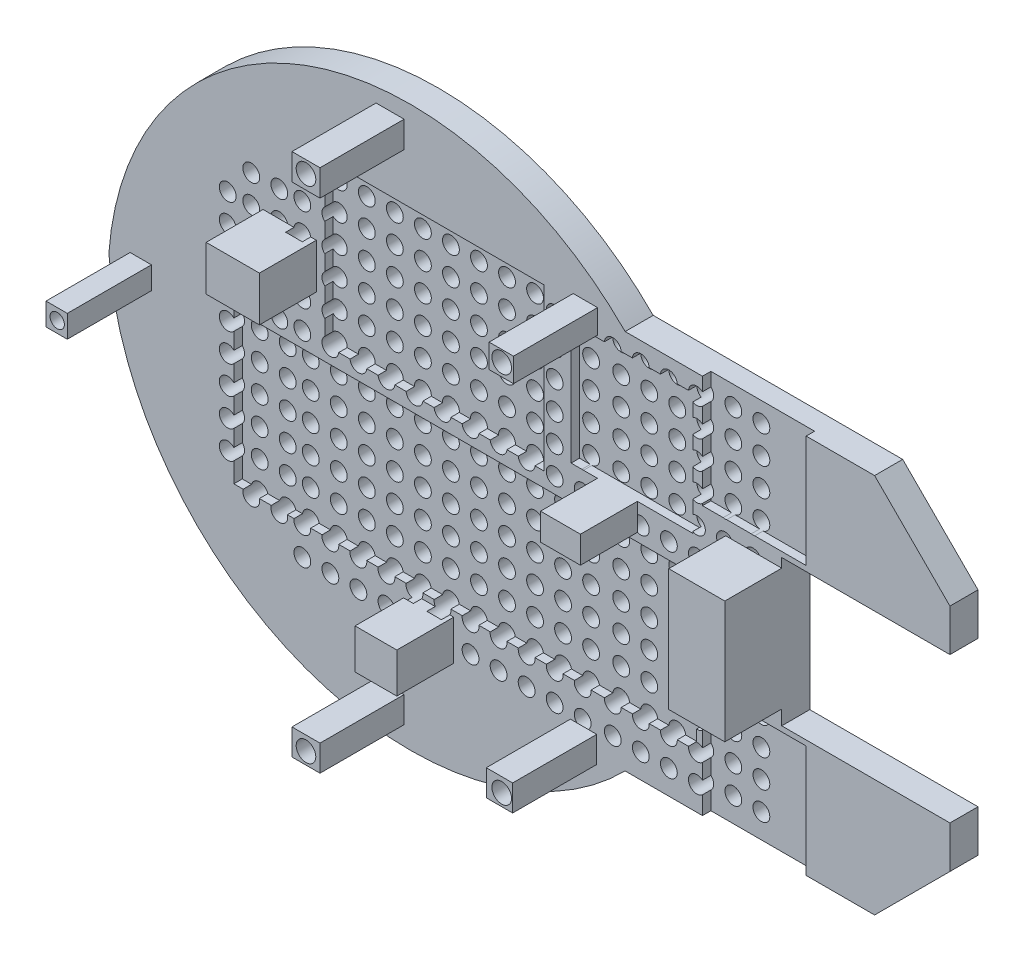
SolidWorks part; units mm, degrees
ref_plane "Front Plane" through (0, 0, 0) normal (0, 0, 1) x (1, 0, 0)
ref_plane "Top Plane" through (0, 0, 0) normal (0, 1, 0) x (1, 0, 0)
ref_plane "Right Plane" through (0, 0, 0) normal (1, 0, 0) x (0, 0, -1)
sketch "Sketch1" plane through (0, 0, 0) normal (0, 0, 1) x (1, 0, 0)
  line L1 (0, 0) -> (0, -26)
  line L2 (0, 26) -> (60, 26)
  line L3 (0, -26) -> (60, -26)
  line L4 (60, 26) -> (60, 41)
  line L5 (60, -26) -> (60, -41)
  line L6 (60, 41) -> (33.1299, 67.8701)
  line L7 (33.1299, 67.8701) -> (-55.8501, 67.8701)
  line L8 (60, -41) -> (33.1299, -67.8701)
  line L9 (33.1299, -67.8701) -> (-55.8501, -67.8701)
  line L10 (-55.8501, 67.8701) -> (-55.8501, 145.9436) construction
  line L11 (-55.8501, 145.9436) -> (-55.8501, -286.005) construction
  line L22 (0, 26) -> (0, 0)
  line L24 (-132.4482, 99.7954) -> (-270.7239, 99.7954) construction
  line L25 (-132.4482, 8.0579) -> (-132.4482, 125.9405) construction
  line L26 (-132.4482, -8.0579) -> (-132.4482, -125.1714) construction
  line L27 (-132.4482, -99.7954) -> (-270.7239, -99.7954) construction
  arc A7 (-240, 0) -> (-55.8501, 67.8701) centre (-132.4482, -8.0579) cw
  arc A8 (-55.8501, -67.8701) -> (-240, 0) centre (-132.4482, 8.0579) cw
  dimension "D11" = 199.5908
  dimension "D12" = 240
  dimension "D10" = 135.7401
  dimension "D1" = 26
  dimension "D2" = 26
  dimension "D3" = 60
  dimension "D4" = 15
  dimension "D5" = 15
  dimension "D6" = 135
  dimension "D7" = 38
  dimension "D8" = 38
  dimension "D9" = 135
  dimension "D15" = 88.98
  dimension "D16" = 88.98
extrude "Boss-Extrude1" add sketch "Sketch1" along normal blind 10 and the other way blind 0.01
sketch "Sketch3" plane through (0, 0, 10) normal (0, 0, 1) x (1, 0, 0)
  line L0 (33.1299, 67.8701) -> (-55.8501, 67.8701) construction
  line L1 (-28.273, 67.8701) -> (8.727, 67.8701)
  line L2 (-28.273, 67.8701) -> (-28.273, 27.8701)
  line L3 (-28.273, 27.8701) -> (8.727, 27.8701)
  line L4 (8.727, 67.8701) -> (8.727, 27.8701)
  dimension "D1" = 40
  dimension "D2" = 37
extrude "Cut-Extrude1" cut sketch "Sketch3" against normal blind 3 contours L2 L1 L4 L3
sketch "Sketch5" plane through (0, 0, 10) normal (0, 0, 1) x (1, 0, 0)
  line L0 (-55.8501, -67.8701) -> (33.1299, -67.8701) construction
  line L1 (-28.273, -27.8701) -> (8.727, -27.8701)
  line L2 (-28.273, -27.8701) -> (-28.273, -67.8701)
  line L3 (-28.273, -67.8701) -> (8.727, -67.8701)
  line L4 (8.727, -27.8701) -> (8.727, -67.8701)
extrude "Cut-Extrude3" cut sketch "Sketch5" against normal blind 3
sketch "Sketch7" plane through (0, 0, 10) normal (0, 0, 1) x (1, 0, 0)
  line L1 (-195.4131, 5.0562) -> (-30.4131, 5.0562)
  line L2 (-195.4131, 5.0562) -> (-195.4131, -48.9438)
  line L3 (-195.4131, -48.9438) -> (-30.4131, -48.9438)
  line L4 (-30.4131, 5.0562) -> (-30.4131, -48.9438)
  dimension "D1" = 54
  dimension "D2" = 165
extrude "Cut-Extrude4" cut sketch "Sketch7" against normal blind 3
sketch "Sketch8" plane through (0, 0, 10) normal (0, 0, 1) x (1, 0, 0)
  line L1 (-162.9927, 67.8133) -> (-84.7927, 67.8133)
  line L2 (-162.9927, 67.8133) -> (-162.9927, 10.3133)
  line L3 (-162.9927, 10.3133) -> (-84.7927, 10.3133)
  line L4 (-84.7927, 67.8133) -> (-84.7927, 10.3133)
  dimension "D1" = 78.2
  dimension "D2" = 57.5
extrude "Cut-Extrude5" cut sketch "Sketch8" against normal blind 3
sketch "Sketch9" plane through (0, 0, 10) normal (0, 0, 1) x (1, 0, 0)
  line L1 (-185, 41) -> (-166, 41)
  line L2 (-185, 41) -> (-185, 25)
  line L3 (-185, 25) -> (-166, 25)
  line L4 (-166, 41) -> (-166, 25)
  line L5 (-65.7317, 21.1542) -> (-51.493, 21.1542)
  line L6 (-65.7317, 21.1542) -> (-65.7317, 8.0108)
  line L7 (-65.7317, 8.0108) -> (-51.493, 8.0108)
  line L8 (-51.493, 21.1542) -> (-51.493, 8.0108)
  line L9 (-131.8867, -50.9252) -> (-116.9909, -50.9252)
  line L10 (-131.8867, -50.9252) -> (-131.8867, -65.1638)
  line L11 (-131.8867, -65.1638) -> (-116.9909, -65.1638)
  line L12 (-116.9909, -50.9252) -> (-116.9909, -65.1638)
extrude "Boss-Extrude2" add sketch "Sketch9" along normal blind 20.3
sketch "Sketch11" plane through (0, 0, -0.01) normal (0, 0, -1) x (-1, 0, 0)
  circle A0 centre (70.989, 60.5844) radius 3
  circle A1 centre (80.989, 60.5844) radius 3
  circle A2 centre (90.989, 60.5844) radius 3
  circle A3 centre (100.989, 60.5844) radius 3
  circle A4 centre (110.989, 60.5844) radius 3
  circle A5 centre (120.989, 60.5844) radius 3
  circle A6 centre (130.989, 60.5844) radius 3
  circle A7 centre (140.989, 60.5844) radius 3
  circle A8 centre (150.989, 60.5844) radius 3
  circle A9 centre (160.989, 60.5844) radius 3
  circle A10 centre (170.989, 60.5844) radius 3
  circle A11 centre (80.989, 50.5844) radius 3
  circle A12 centre (90.989, 50.5844) radius 3
  circle A13 centre (100.989, 50.5844) radius 3
  circle A14 centre (110.989, 50.5844) radius 3
  circle A15 centre (120.989, 50.5844) radius 3
  circle A16 centre (130.989, 50.5844) radius 3
  circle A17 centre (140.989, 50.5844) radius 3
  circle A18 centre (150.989, 50.5844) radius 3
  circle A19 centre (160.989, 50.5844) radius 3
  circle A20 centre (170.989, 50.5844) radius 3
  circle A21 centre (80.989, 40.5844) radius 3
  circle A22 centre (90.989, 40.5844) radius 3
  circle A23 centre (100.989, 40.5844) radius 3
  circle A24 centre (110.989, 40.5844) radius 3
  circle A25 centre (120.989, 40.5844) radius 3
  circle A26 centre (130.989, 40.5844) radius 3
  circle A27 centre (140.989, 40.5844) radius 3
  circle A28 centre (150.989, 40.5844) radius 3
  circle A29 centre (160.989, 40.5844) radius 3
  circle A30 centre (170.989, 40.5844) radius 3
  circle A31 centre (80.989, 30.5844) radius 3
  circle A32 centre (90.989, 30.5844) radius 3
  circle A33 centre (100.989, 30.5844) radius 3
  circle A34 centre (110.989, 30.5844) radius 3
  circle A35 centre (120.989, 30.5844) radius 3
  circle A36 centre (130.989, 30.5844) radius 3
  circle A37 centre (140.989, 30.5844) radius 3
  circle A38 centre (150.989, 30.5844) radius 3
  circle A39 centre (160.989, 30.5844) radius 3
  circle A40 centre (170.989, 30.5844) radius 3
  circle A41 centre (80.989, 20.5844) radius 3
  circle A42 centre (90.989, 20.5844) radius 3
  circle A43 centre (100.989, 20.5844) radius 3
  circle A44 centre (110.989, 20.5844) radius 3
  circle A45 centre (120.989, 20.5844) radius 3
  circle A46 centre (130.989, 20.5844) radius 3
  circle A47 centre (140.989, 20.5844) radius 3
  circle A48 centre (150.989, 20.5844) radius 3
  circle A49 centre (160.989, 20.5844) radius 3
  circle A50 centre (170.989, 20.5844) radius 3
  circle A51 centre (80.989, 10.5844) radius 3
  circle A52 centre (90.989, 10.5844) radius 3
  circle A53 centre (100.989, 10.5844) radius 3
  circle A54 centre (110.989, 10.5844) radius 3
  circle A55 centre (120.989, 10.5844) radius 3
  circle A56 centre (130.989, 10.5844) radius 3
  circle A57 centre (140.989, 10.5844) radius 3
  circle A58 centre (150.989, 10.5844) radius 3
  circle A59 centre (160.989, 10.5844) radius 3
  circle A60 centre (170.989, 10.5844) radius 3
  circle A61 centre (80.989, 0.5844) radius 3
  circle A62 centre (90.989, 0.5844) radius 3
  circle A63 centre (100.989, 0.5844) radius 3
  circle A64 centre (110.989, 0.5844) radius 3
  circle A65 centre (120.989, 0.5844) radius 3
  circle A66 centre (130.989, 0.5844) radius 3
  circle A67 centre (140.989, 0.5844) radius 3
  circle A68 centre (150.989, 0.5844) radius 3
  circle A69 centre (160.989, 0.5844) radius 3
  circle A70 centre (170.989, 0.5844) radius 3
  circle A71 centre (80.989, -9.4156) radius 3
  circle A72 centre (90.989, -9.4156) radius 3
  circle A73 centre (100.989, -9.4156) radius 3
  circle A74 centre (110.989, -9.4156) radius 3
  circle A75 centre (120.989, -9.4156) radius 3
  circle A76 centre (130.989, -9.4156) radius 3
  circle A77 centre (140.989, -9.4156) radius 3
  circle A78 centre (150.989, -9.4156) radius 3
  circle A79 centre (160.989, -9.4156) radius 3
  circle A80 centre (170.989, -9.4156) radius 3
  circle A81 centre (80.989, -19.4156) radius 3
  circle A82 centre (90.989, -19.4156) radius 3
  circle A83 centre (100.989, -19.4156) radius 3
  circle A84 centre (110.989, -19.4156) radius 3
  circle A85 centre (120.989, -19.4156) radius 3
  circle A86 centre (130.989, -19.4156) radius 3
  circle A87 centre (140.989, -19.4156) radius 3
  circle A88 centre (150.989, -19.4156) radius 3
  circle A89 centre (160.989, -19.4156) radius 3
  circle A90 centre (170.989, -19.4156) radius 3
  circle A91 centre (80.989, -29.4156) radius 3
  circle A92 centre (90.989, -29.4156) radius 3
  circle A93 centre (100.989, -29.4156) radius 3
  circle A94 centre (110.989, -29.4156) radius 3
  circle A95 centre (120.989, -29.4156) radius 3
  circle A96 centre (130.989, -29.4156) radius 3
  circle A97 centre (140.989, -29.4156) radius 3
  circle A98 centre (150.989, -29.4156) radius 3
  circle A99 centre (160.989, -29.4156) radius 3
  circle A100 centre (170.989, -29.4156) radius 3
  circle A101 centre (80.989, -39.4156) radius 3
  circle A102 centre (90.989, -39.4156) radius 3
  circle A103 centre (100.989, -39.4156) radius 3
  circle A104 centre (110.989, -39.4156) radius 3
  circle A105 centre (120.989, -39.4156) radius 3
  circle A106 centre (130.989, -39.4156) radius 3
  circle A107 centre (140.989, -39.4156) radius 3
  circle A108 centre (150.989, -39.4156) radius 3
  circle A109 centre (160.989, -39.4156) radius 3
  circle A110 centre (170.989, -39.4156) radius 3
  circle A111 centre (80.989, -49.4156) radius 3
  circle A112 centre (90.989, -49.4156) radius 3
  circle A113 centre (100.989, -49.4156) radius 3
  circle A114 centre (110.989, -49.4156) radius 3
  circle A115 centre (120.989, -49.4156) radius 3
  circle A116 centre (130.989, -49.4156) radius 3
  circle A117 centre (140.989, -49.4156) radius 3
  circle A118 centre (150.989, -49.4156) radius 3
  circle A119 centre (160.989, -49.4156) radius 3
  circle A120 centre (170.989, -49.4156) radius 3
  circle A121 centre (80.989, -59.4156) radius 3
  circle A122 centre (90.989, -59.4156) radius 3
  circle A123 centre (100.989, -59.4156) radius 3
  circle A124 centre (110.989, -59.4156) radius 3
  circle A125 centre (120.989, -59.4156) radius 3
  circle A126 centre (130.989, -59.4156) radius 3
  circle A127 centre (140.989, -59.4156) radius 3
  circle A128 centre (150.989, -59.4156) radius 3
  circle A129 centre (160.989, -59.4156) radius 3
  circle A130 centre (170.989, -59.4156) radius 3
  circle A131 centre (70.989, 50.5844) radius 3
  circle A132 centre (70.989, 40.5844) radius 3
  circle A133 centre (70.989, 30.5844) radius 3
  circle A134 centre (70.989, 20.5844) radius 3
  circle A135 centre (70.989, 10.5844) radius 3
  circle A136 centre (70.989, 0.5844) radius 3
  circle A137 centre (70.989, -9.4156) radius 3
  circle A138 centre (70.989, -19.4156) radius 3
  circle A139 centre (70.989, -29.4156) radius 3
  circle A140 centre (70.989, -39.4156) radius 3
  circle A141 centre (70.989, -49.4156) radius 3
  circle A142 centre (70.989, -59.4156) radius 3
  dimension "D1" = 11
  dimension "D2" = 13
extrude "Cut-Extrude12" cut sketch "Sketch11" against normal blind 13
sketch "Sketch12" plane through (0, 0, -0.01) normal (0, 0, -1) x (-1, 0, 0)
  circle A0 centre (179.2029, 50.2603) radius 3
  circle A1 centre (189.2029, 50.2603) radius 3
  circle A2 centre (189.2029, 40.2603) radius 3
  circle A3 centre (189.2029, 30.2603) radius 3
  circle A4 centre (189.2029, 20.2603) radius 3
  circle A5 centre (189.2029, 10.2603) radius 3
  circle A6 centre (189.2029, 0.2603) radius 3
  circle A7 centre (189.2029, -9.7397) radius 3
  circle A8 centre (189.2029, -19.7397) radius 3
  circle A9 centre (189.2029, -29.7397) radius 3
  circle A10 centre (189.2029, -39.7397) radius 3
  circle A11 centre (189.2029, -49.7397) radius 3
  circle A12 centre (179.2029, 40.2603) radius 3
  circle A13 centre (179.2029, 30.2603) radius 3
  circle A14 centre (179.2029, 20.2603) radius 3
  circle A15 centre (179.2029, 10.2603) radius 3
  circle A16 centre (179.2029, 0.2603) radius 3
  circle A17 centre (179.2029, -9.7397) radius 3
  circle A18 centre (179.2029, -19.7397) radius 3
  circle A19 centre (179.2029, -29.7397) radius 3
  circle A20 centre (179.2029, -39.7397) radius 3
  circle A21 centre (179.2029, -49.7397) radius 3
  dimension "D1" = 2
  dimension "D2" = 11
extrude "Cut-Extrude13" cut sketch "Sketch12" against normal up to surface (10.01 mm away) up to face at (-153.989, -59.4156, 10)
sketch "Sketch13" plane through (0, 0, -0.01) normal (0, 0, -1) x (-1, 0, 0)
  circle A0 centre (197.6037, 40.2121) radius 3
  circle A1 centre (197.6037, 30.2121) radius 3
  circle A2 centre (197.6037, 20.2121) radius 3
  circle A3 centre (197.6037, 10.2121) radius 3
  circle A4 centre (197.6037, 0.2121) radius 3
  circle A5 centre (197.6037, -9.7879) radius 3
  circle A6 centre (197.6037, -19.7879) radius 3
  circle A7 centre (197.6037, -29.7879) radius 3
  circle A8 centre (197.6037, -39.7879) radius 3
  dimension "D1" = 9
extrude "Cut-Extrude14" cut sketch "Sketch13" against normal up to surface (10.01 mm away) up to face at (-182.2029, 20.2603, 10)
sketch "Sketch14" plane through (0, 0, -0.01) normal (0, 0, -1) x (-1, 0, 0)
  circle A0 centre (60.2552, 60.8035) radius 3
  circle A1 centre (50.2552, 60.8035) radius 3
  circle A2 centre (40.2552, 60.8035) radius 3
  circle A3 centre (30.2552, 60.8035) radius 3
  circle A4 centre (20.2552, 60.8035) radius 3
  circle A5 centre (10.2552, 60.8035) radius 3
  circle A6 centre (50.2552, 50.8035) radius 3
  circle A7 centre (40.2552, 50.8035) radius 3
  circle A8 centre (30.2552, 50.8035) radius 3
  circle A9 centre (20.2552, 50.8035) radius 3
  circle A10 centre (10.2552, 50.8035) radius 3
  circle A11 centre (50.2552, 40.8035) radius 3
  circle A12 centre (40.2552, 40.8035) radius 3
  circle A13 centre (30.2552, 40.8035) radius 3
  circle A14 centre (20.2552, 40.8035) radius 3
  circle A15 centre (10.2552, 40.8035) radius 3
  circle A16 centre (50.2552, 30.8035) radius 3
  circle A17 centre (40.2552, 30.8035) radius 3
  circle A18 centre (30.2552, 30.8035) radius 3
  circle A19 centre (20.2552, 30.8035) radius 3
  circle A20 centre (10.2552, 30.8035) radius 3
  circle A21 centre (50.2552, 20.8035) radius 3
  circle A22 centre (40.2552, 20.8035) radius 3
  circle A23 centre (30.2552, 20.8035) radius 3
  circle A24 centre (20.2552, 20.8035) radius 3
  circle A25 centre (10.2552, 20.8035) radius 3
  circle A26 centre (50.2552, 10.8035) radius 3
  circle A27 centre (40.2552, 10.8035) radius 3
  circle A28 centre (30.2552, 10.8035) radius 3
  circle A29 centre (20.2552, 10.8035) radius 3
  circle A30 centre (10.2552, 10.8035) radius 3
  circle A31 centre (50.2552, 0.8035) radius 3
  circle A32 centre (40.2552, 0.8035) radius 3
  circle A33 centre (30.2552, 0.8035) radius 3
  circle A34 centre (20.2552, 0.8035) radius 3
  circle A35 centre (10.2552, 0.8035) radius 3
  circle A36 centre (50.2552, -9.1965) radius 3
  circle A37 centre (40.2552, -9.1965) radius 3
  circle A38 centre (30.2552, -9.1965) radius 3
  circle A39 centre (20.2552, -9.1965) radius 3
  circle A40 centre (10.2552, -9.1965) radius 3
  circle A41 centre (50.2552, -19.1965) radius 3
  circle A42 centre (40.2552, -19.1965) radius 3
  circle A43 centre (30.2552, -19.1965) radius 3
  circle A44 centre (20.2552, -19.1965) radius 3
  circle A45 centre (10.2552, -19.1965) radius 3
  circle A46 centre (50.2552, -29.1965) radius 3
  circle A47 centre (40.2552, -29.1965) radius 3
  circle A48 centre (30.2552, -29.1965) radius 3
  circle A49 centre (20.2552, -29.1965) radius 3
  circle A50 centre (10.2552, -29.1965) radius 3
  circle A51 centre (50.2552, -39.1965) radius 3
  circle A52 centre (40.2552, -39.1965) radius 3
  circle A53 centre (30.2552, -39.1965) radius 3
  circle A54 centre (20.2552, -39.1965) radius 3
  circle A55 centre (10.2552, -39.1965) radius 3
  circle A56 centre (50.2552, -49.1965) radius 3
  circle A57 centre (40.2552, -49.1965) radius 3
  circle A58 centre (30.2552, -49.1965) radius 3
  circle A59 centre (20.2552, -49.1965) radius 3
  circle A60 centre (10.2552, -49.1965) radius 3
  circle A61 centre (50.2552, -59.1965) radius 3
  circle A62 centre (40.2552, -59.1965) radius 3
  circle A63 centre (30.2552, -59.1965) radius 3
  circle A64 centre (20.2552, -59.1965) radius 3
  circle A65 centre (10.2552, -59.1965) radius 3
  circle A66 centre (60.2552, 50.8035) radius 3
  circle A67 centre (60.2552, 40.8035) radius 3
  circle A68 centre (60.2552, 30.8035) radius 3
  circle A69 centre (60.2552, 20.8035) radius 3
  circle A70 centre (60.2552, 10.8035) radius 3
  circle A71 centre (60.2552, 0.8035) radius 3
  circle A72 centre (60.2552, -9.1965) radius 3
  circle A73 centre (60.2552, -19.1965) radius 3
  circle A74 centre (60.2552, -29.1965) radius 3
  circle A75 centre (60.2552, -39.1965) radius 3
  circle A76 centre (60.2552, -49.1965) radius 3
  circle A77 centre (60.2552, -59.1965) radius 3
  dimension "D1" = 6
  dimension "D2" = 13
extrude "Cut-Extrude16" cut sketch "Sketch14" against normal up to surface (10.01 mm away) up to face at (-200.6037, 40.2121, 10)
sketch "Sketch15" plane through (0, 0, 10) normal (0, 0, 1) x (1, 0, 0)
  line L0 (0, -26) -> (0, 26) construction
  line L1 (-20, 22.7016) -> (0, 22.7016)
  line L2 (-20, 22.7016) -> (-20, -20.7984)
  line L3 (-20, -20.7984) -> (0, -20.7984)
  line L4 (0, 22.7016) -> (0, -20.7984)
  dimension "D1" = 43.5
  dimension "D2" = 20
extrude "Boss-Extrude3" add sketch "Sketch15" along normal blind 20.3
sketch "Sketch4" plane through (0, 0, 7) normal (0, 0, 1) x (1, 0, 0)
  line L1 (-28.3661, -27.8728) -> (8.6339, -27.8728)
  line L2 (-28.3661, -27.8728) -> (-28.3661, -67.8728)
  line L3 (-28.3661, -67.8728) -> (8.6339, -67.8728)
  line L4 (8.6339, -27.8728) -> (8.6339, -67.8728)
  dimension "D1" = 40
  dimension "D2" = 37
sketch "Sketch16" plane through (0, 0, 10) normal (0, 0, 1) x (1, 0, 0)
  line L1 (-232.4208, 4) -> (-224.8235, 4)
  line L2 (-232.4208, 4) -> (-232.4208, -4)
  line L3 (-232.4208, -4) -> (-224.8235, -4)
  line L4 (-224.8235, 4) -> (-224.8235, -4)
  line L9 (-134.6881, 94.0493) -> (-144.6881, 94.0493)
  line L10 (-134.6881, 94.0493) -> (-134.6881, 84.6493)
  line L11 (-134.6881, 84.6493) -> (-144.6881, 84.6493)
  line L12 (-144.6881, 94.0493) -> (-144.6881, 84.6493)
  line L13 (-65.6779, 70.3488) -> (-74.3779, 70.3488)
  line L14 (-65.6779, 70.3488) -> (-65.6779, 61.8488)
  line L15 (-65.6779, 61.8488) -> (-74.3779, 61.8488)
  line L16 (-74.3779, 70.3488) -> (-74.3779, 61.8488)
  line L17 (-65.9779, -61.6233) -> (-75.3779, -61.6233)
  line L18 (-65.9779, -61.6233) -> (-65.9779, -70.9233)
  line L19 (-65.9779, -70.9233) -> (-75.3779, -70.9233)
  line L20 (-75.3779, -61.6233) -> (-75.3779, -70.9233)
  line L21 (-134.6881, -83.6815) -> (-144.6881, -83.6815)
  line L22 (-134.6881, -83.6815) -> (-134.6881, -92.9815)
  line L23 (-134.6881, -92.9815) -> (-144.6881, -92.9815)
  line L24 (-144.6881, -83.6815) -> (-144.6881, -92.9815)
  point P4 (0, 0)
  point P5 (0, 0)
  point P6 (0, 0)
  point P7 (0, 0)
  point P24 (0, 0)
  point P25 (0, 0)
  point P26 (0, 0)
  point P27 (0, 0)
  point P28 (0, 0)
  point P29 (0, 0)
  point P30 (0, 0)
  point P31 (0, 0)
  point P32 (0, 0)
  point P33 (0, 0)
  point P34 (0, 0)
  point P35 (0, 0)
  point P36 (0, 0)
  point P37 (0, 0)
  point P38 (0, 0)
  point P39 (0, 0)
  point P40 (0, 0)
  point P41 (0, 0)
  point P42 (0, 0)
  point P43 (0, 0)
  point P44 (0, 0)
  point P45 (0, 0)
  point P46 (0, 0)
  point P47 (0, 0)
  point P48 (0, 0)
  point P49 (0, 0)
  point P50 (0, 0)
  point P51 (0, 0)
  point P52 (0, 0)
  point P53 (0, 0)
  point P54 (0, 0)
extrude "Boss-Extrude4" add sketch "Sketch16" along normal blind 30
sketch "Sketch17" plane through (0, 0, 0) normal (0, 0, 1) x (1, 0, 0)
  circle A1 centre (-228.4208, 0) radius 2.55
  circle A2 centre (-139.6881, 89.6493) radius 3.5
  circle A3 centre (-69.8779, 66.3488) radius 3.5
  circle A4 centre (-69.8779, -66.6233) radius 3.5
  circle A5 centre (-139.6881, -88.6815) radius 3.5
  point P0 (0, 0)
  point P14 (0, 0)
  point P15 (0, 0)
  point P16 (0, 0)
  point P17 (0, 0)
extrude "Cut-Extrude17" cut sketch "Sketch17" along normal through all
sketch "Sketch18" plane through (0, 0, 10) normal (0, 0, 1) x (1, 0, 0)
  line L1 (-75.1245, 61) -> (-31.7245, 61)
  line L2 (-75.1245, 61) -> (-75.1245, 17.6)
  line L3 (-75.1245, 17.6) -> (-31.7245, 17.6)
  line L4 (-31.7245, 61) -> (-31.7245, 17.6)
  dimension "D1" = 43.4
  dimension "43.4" = 43.4
extrude "Cut-Extrude18" cut sketch "Sketch18" against normal blind 3
sketch "Sketch19" plane through (0, 0, 30.3) normal (0, 0, 1) x (1, 0, 0)
  line L0 (-65.7317, 17.6) -> (-51.493, 17.6)
  line L1 (-51.493, 17.6) -> (-51.493, 21.1542)
  line L2 (-51.493, 21.1542) -> (-65.7317, 21.1542)
  line L3 (-65.7317, 21.1542) -> (-65.7317, 17.6)
extrude "Cut-Extrude19" cut sketch "Sketch19" against normal up to surface (23.3 mm away) up to face at (-57.2552, 50.8035, 7)
